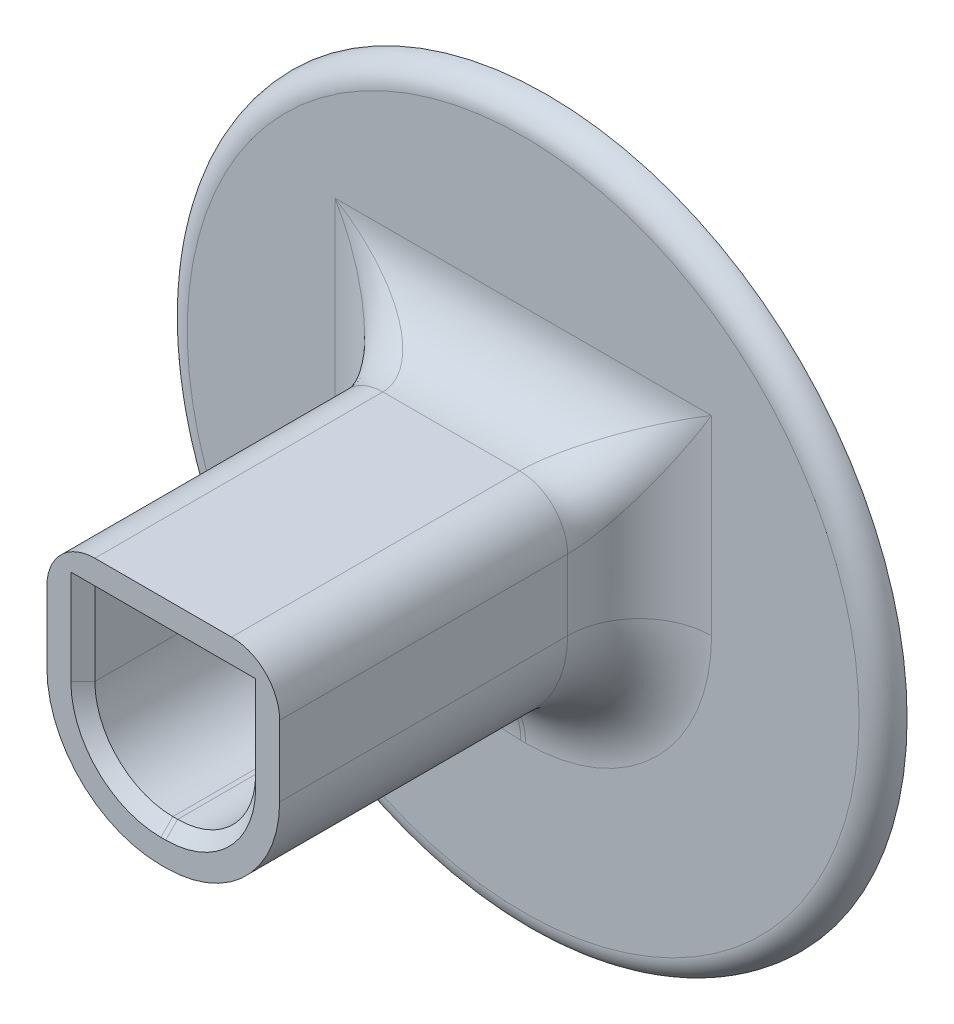
SolidWorks part; units mm, degrees
ref_plane "Alzado" through (0, 0, 0) normal (0, 0, 1) x (1, 0, 0)
ref_plane "Planta" through (0, 0, 0) normal (0, 1, 0) x (1, 0, 0)
ref_plane "Vista lateral" through (0, 0, 0) normal (1, 0, 0) x (0, 0, -1)
sketch "Croquis1" plane through (0, 0, 0) normal (0, 0, 1) x (1, 0, 0)
  circle A0 centre (0, 0) radius 15
  dimension "D1" = 30
extrude "Saliente-Extruir1" add sketch "Croquis1" along normal blind 1
sketch "Croquis2" plane through (0, 0, 1) normal (0, 0, 1) x (1, 0, 0)
  line L0 (-4.85, 4.85) -> (4.85, 4.85)
  line L1 (-3.35, 3.35) -> (3.35, 3.35)
  line L2 (-3.35, 3.35) -> (-3.35, -0.1)
  line L3 (-0.1, -3.35) -> (0.1, -3.35)
  line L4 (3.35, 3.35) -> (3.35, -0.1)
  line L5 (4.85, 4.85) -> (4.85, -0.1)
  line L6 (-0.1, -4.85) -> (0.1, -4.85)
  line L7 (-4.85, 4.85) -> (-4.85, -0.1)
  arc A0 (3.35, -0.1) -> (0.1, -3.35) centre (0.1, -0.1) cw
  arc A1 (-0.1, -3.35) -> (-3.35, -0.1) centre (-0.1, -0.1) cw
  arc A2 (4.85, -0.1) -> (0.1, -4.85) centre (0.1, -0.1) cw
  arc A3 (-0.1, -4.85) -> (-4.85, -0.1) centre (-0.1, -0.1) cw
  point P7 (3.35, -3.35)
  dimension "D5" = 3.25
  dimension "D1" = 6.7
  dimension "D2" = 6.7
  dimension "D3" = 3.35
  dimension "D4" = 3.35
  dimension "D6" = 1.5
extrude "Saliente-Extruir2" add sketch "Croquis2" along normal blind 15
fillet "Redondeo1" radius 3 6 edges at (-4.85, 2.375, 1) (-3.4588, -3.4588, 1) (0, -4.85, 1) (3.4588, -3.4588, 1) (0, 4.85, 1) (4.85, 2.375, 1)
fillet "Redondeo2" radius 2 4 edges at (-5.7287, 5.7287, 1.8787) (5.7287, 5.7287, 1.8787) (-4.85, 4.85, 10) (4.85, 4.85, 10)
chamfer "Chaflán1" distance 0.5 angle 45 6 edges at (3.35, 1.625, 16) (2.3981, -2.3981, 16) (0, -3.35, 16) (-2.3981, -2.3981, 16) (-3.35, 1.625, 16) (0, 3.35, 16)
fillet "Redondeo3" radius 1 1 edges at (15, 0, 1)
equation "\"D1@Croquis2\"=\"D2@Croquis2\""
